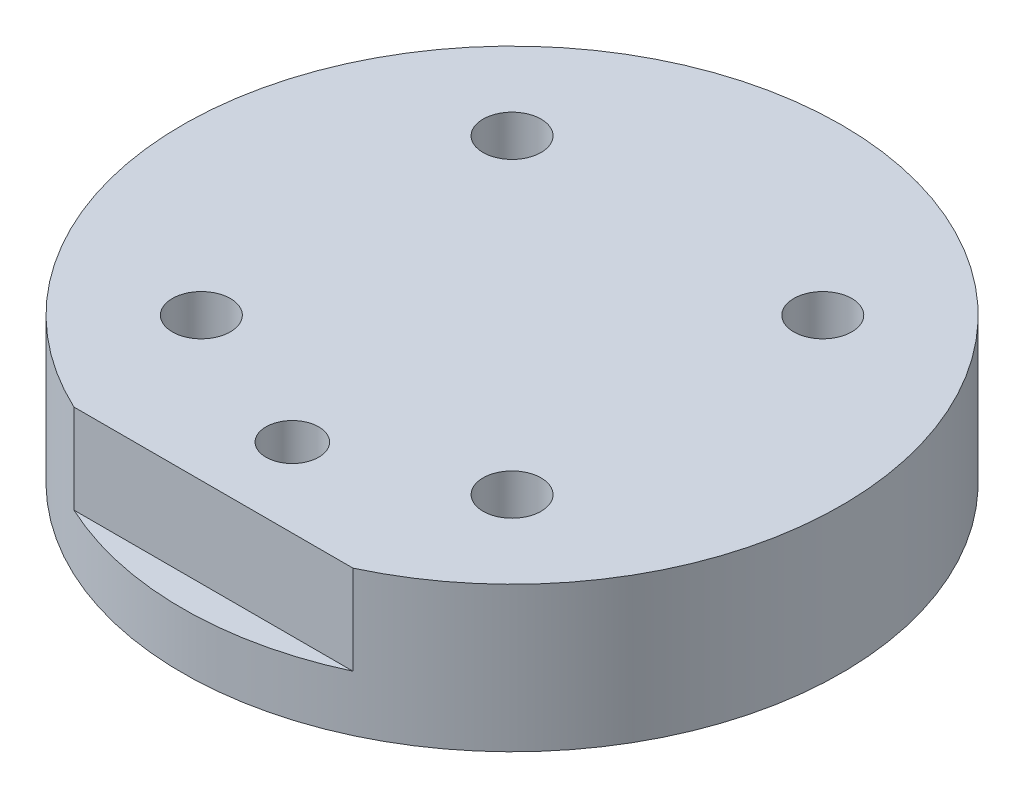
SolidWorks part; units mm, degrees
ref_plane "Front Plane" through (0, 0, 0) normal (0, 0, 1) x (1, 0, 0)
ref_plane "Top Plane" through (0, 0, 0) normal (0, 1, 0) x (1, 0, 0)
ref_plane "Right Plane" through (0, 0, 0) normal (1, 0, 0) x (0, 0, -1)
sketch "Sketch1" plane through (0, 0, 0) normal (0, 1, 0) x (1, 0, 0)
  line L0 (-37.5, 0) -> (37.5, 0) construction
  line L5 (-27.305, -16.1925) -> (27.305, -16.1925) construction
  line L6 (-27.305, -16.1925) -> (-27.305, 16.1925) construction
  line L7 (-27.305, 16.1925) -> (27.305, 16.1925) construction
  line L8 (27.305, -16.1925) -> (27.305, 16.1925) construction
  line L9 (-27.305, -16.1925) -> (27.305, 16.1925) construction
  line L10 (-27.305, 16.1925) -> (27.305, -16.1925) construction
  line L11 (-18.9072, 3.175) -> (-6.2072, 3.175)
  line L12 (-18.9072, 3.175) -> (-18.9072, -3.175)
  line L13 (-18.9072, -3.175) -> (-6.2072, -3.175)
  line L14 (-6.2072, 3.175) -> (-6.2072, -3.175)
  line L15 (-18.9072, 3.175) -> (-6.2072, -3.175) construction
  line L16 (-18.9072, -3.175) -> (-6.2072, 3.175) construction
  circle A0 centre (27.305, 16.1925) radius 2.5
  circle A1 centre (27.305, -16.1925) radius 2.5
  circle A2 centre (-27.305, -16.1925) radius 2.5
  circle A3 centre (-27.305, 16.1925) radius 2.5
  circle A4 centre (0, 0) radius 37.5
  circle A5 centre (-30.515, 0) radius 1.9685
  point P0 (0, 0)
  point P12 (-12.5572, 0)
  point P19 (17.6777, 17.6777)
  point P20 (17.6777, -17.6777)
  point P23 (-17.6777, -17.6777)
  point P24 (-17.6777, 17.6777)
  point P25 (17.5297, 17.8244)
  point P26 (-16.5456, 18.7415)
  point P27 (0, 0)
  arc B0 (0, 15.75) -> (0, -15.75) centre (0, 0) ccw construction
  arc B1 (0, -15.75) -> (0, 15.75) centre (0, 0) ccw construction
  arc B2 (0, 22) -> (0, 28) centre (0, 25) ccw construction
  arc B3 (0, 28) -> (0, 22) centre (0, 25) ccw construction
  arc B4 (17.6777, 15.1777) -> (17.6777, 20.1777) centre (17.6777, 17.6777) ccw construction
  arc B5 (17.6777, 20.1777) -> (17.6777, 15.1777) centre (17.6777, 17.6777) ccw construction
  arc B6 (17.6777, -20.1777) -> (17.6777, -15.1777) centre (17.6777, -17.6777) ccw construction
  arc B7 (17.6777, -15.1777) -> (17.6777, -20.1777) centre (17.6777, -17.6777) ccw construction
  arc B8 (-17.6777, -20.1777) -> (-17.6777, -15.1777) centre (-17.6777, -17.6777) ccw construction
  arc B9 (-17.6777, -15.1777) -> (-17.6777, -20.1777) centre (-17.6777, -17.6777) ccw construction
  arc B10 (-17.6777, 20.1777) -> (-17.6777, 15.1777) centre (-17.6777, 17.6777) ccw construction
  arc B11 (-17.6777, 15.1777) -> (-17.6777, 20.1777) centre (-17.6777, 17.6777) ccw construction
  arc B12 (0, -35) -> (0, 35) centre (0, 0) ccw construction
  arc B13 (0, 35) -> (0, -35) centre (0, 0) ccw construction
  arc B14 (0, -31.5) -> (0, 31.5) centre (0, 0) ccw construction
  arc B15 (0, 31.5) -> (0, -31.5) centre (0, 0) ccw construction
  arc B16 (0, -37.5) -> (0, 37.5) centre (0, 0) ccw construction
  arc B17 (0, 37.5) -> (0, -37.5) centre (0, 0) ccw construction
  dimension "D3" = 5
  dimension "D7" = 3.937
  dimension "D1" = 32.385
  dimension "D2" = 54.61
  dimension "D4" = 12.7
  dimension "D5" = 31.2928
  dimension "D6" = 6.35
  dimension "D8" = 6.985
sketch_block_instance "UR5 attach pattern-1"
sketch_block "UR5 attach pattern"
sketch "Sketch2" plane through (0, 0, 0) normal (0, 1, 0) x (1, 0, 0)
  circle A0 centre (0, 0) radius 37.5
extrude "Boss-Extrude1" add sketch "Sketch2" along normal blind 13.97
sketch "Sketch3" [suppressed] plane through (0, 0, 0) normal (0, -1, 0) x (1, 0, 0)
  line L0 (-37.5, 0) -> (37.5, 0) construction
  line L1 (34.925, 7.4711) -> (-34.925, 7.4711)
  line L2 (34.925, 7.4711) -> (34.925, -7.4711)
  line L3 (34.925, -7.4711) -> (-34.925, -7.4711)
  line L4 (-34.925, 7.4711) -> (-34.925, -7.4711)
  line L5 (34.925, 7.4711) -> (-34.925, -7.4711) construction
  line L6 (34.925, -7.4711) -> (-34.925, 7.4711) construction
  point P0 (0, 0)
hole_wizard "CSK for M6 Flat Head Machine Screw1" positions "Sketch4" profile "Sketch5" countersink size "M6" standard "ANSI Metric" end condition through all
sketch "Sketch4" plane through (0, 0, 0) normal (0, -1, 0) x (-1, 0, 0)
  point P0 (-17.6777, 17.6777)
  point P3 (17.6777, 17.6777)
  point P6 (17.6777, -17.6777)
  point P9 (-17.6777, -17.6777)
sketch "Sketch5" plane through (17.6777, 0, -17.6777) normal (1, 0, 0) x (0, 0, -1)
  line L0 (0, 0) -> (0, 13.97)
  line L1 (0, 13.97) -> (3.3, 13.97)
  line L2 (3.3, 13.97) -> (3.3, 3)
  line L3 (3.3, 3) -> (6.3, 0)
  line L5 (6.3, 0) -> (0, 0)
  line L6 (-3.3, 3) -> (-6.3, 0) construction
  line L11 (0, -6.35) -> (0, 107.95) construction
  dimension "Thru Hole Dia." = 6.6
  dimension "Thru Hole Depth" = 13.97
  dimension "Near C'Sink Dia." = 12.6
  dimension "Near C'Sink Angle" = 90
hole_wizard "M5x0.8 Tapped Hole1" positions "Sketch6" profile "Sketch7" tap size "M5x0.8" standard "ANSI Metric"
sketch "Sketch6" plane through (0, 0, 0) normal (0, -1, 0) x (-1, 0, 0)
  point P0 (-27.305, 16.1925)
  point P3 (-27.305, -16.1925)
  point P6 (27.305, -16.1925)
  point P9 (27.305, 16.1925)
sketch "Sketch7" plane through (27.305, 0, -16.1925) normal (1, 0, 0) x (0, 0, -1)
  line L0 (0, 0) -> (0, 13.4538)
  line L1 (0, 13.4538) -> (2.1, 12.192)
  line L2 (2.1, 12.192) -> (2.1, 0)
  line L5 (2.1, 0) -> (0, 0)
  line L10 (0, 13.4538) -> (-2.1, 12.192) construction
  line L11 (0, -6.35) -> (0, 107.95) construction
  dimension "Tap Drill Dia." = 4.2
  dimension "Tap Drill Depth" = 12.192
  dimension "Drill Angle" = 118
cosmetic thread "Hole Thread1" parameters "D1"=9.906, "D2"=5
cosmetic thread "Hole Thread2" parameters "D1"=9.906, "D2"=5
cosmetic thread "Hole Thread3" parameters "D1"=9.906, "D2"=5
cosmetic thread "Hole Thread4" parameters "D1"=9.906, "D2"=5
extrude "Cut-Extrude1" cut sketch "Sketch1" along normal blind 5.08 contours A5
extrude "Pogo pins" add sketch "Sketch1<3>" against normal blind 3.048 contours L11 L14 L13 L12
sketch "Sketch1<3>" plane through (0, 0, 0) normal (0, 1, 0) x (1, 0, 0) same geometry as "Sketch1"
sketch "Sketch8" plane through (0, 13.97, 0) normal (0, 1, 0) x (1, 0, 0)
  line L0 (37.5, 0) -> (-37.5, 0) construction
  line L1 (15.875, -33.974) -> (-15.875, -33.974)
  circle A0 centre (0, 25) radius 3 construction
  arc A1 (0, 22) -> (0, 28) centre (0, 25) ccw construction
  circle A2 centre (0, 0) radius 37.5 construction
  circle A3 centre (0, -25) radius 3
  circle A5 centre (0, 0) radius 37.5
  circle A6 centre (0, 0) radius 37.5
  point P0 (0, 25)
  circle M6 centre (0, 0) radius 37.5
  dimension "D2" = 31.75
  dimension "D1" = 0
extrude "Cut-Extrude2" cut sketch "Sketch8" against normal blind 10.16 contours A3 | L1 M6 region at (0, 13.97, 35.3903) region at (0, 13.97, 25)
sketch "Sketch9" plane through (0, 0, 0) normal (0, -1, 0) x (1, 0, 0)
  circle A0 centre (0, 0) radius 37.5
  circle A1 centre (0, 0) radius 37.5 construction
  circle A2 centre (0, 0) radius 34.96
  dimension "D1" = 2.54
extrude "Lip" add sketch "Sketch9" along normal blind 2.54
chamfer "Chamfer1" distance 0.508 angle 45 1 edges at (0, -2.54, -34.96)
